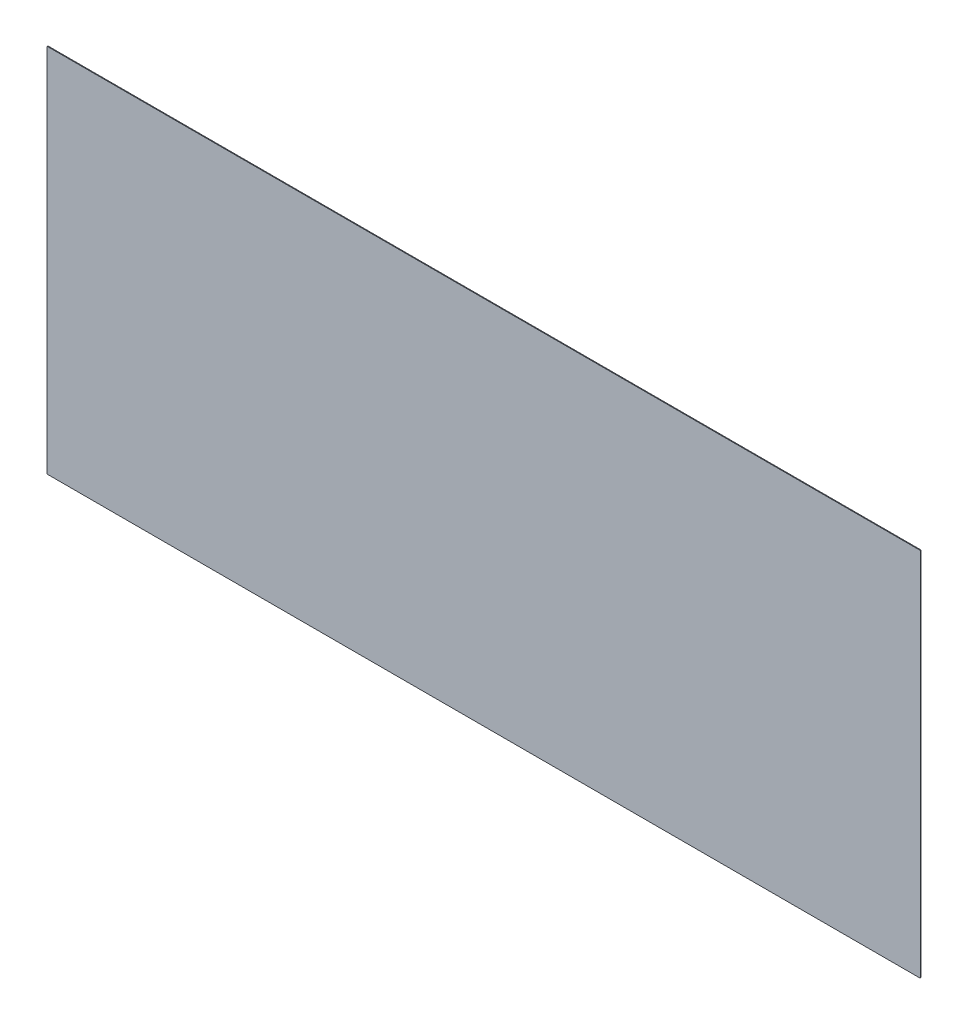
SolidWorks part; units mm, degrees
ref_plane "Front Plane" through (0, 0, 0) normal (0, 0, 1) x (1, 0, 0)
ref_plane "Top Plane" through (0, 0, 0) normal (0, 1, 0) x (1, 0, 0)
ref_plane "Right Plane" through (0, 0, 0) normal (1, 0, 0) x (0, 0, -1)
sketch "Sketch1" plane through (0, 0, 0) normal (0, 0, 1) x (1, 0, 0)
  line L1 (1, 0) -> (1159, 0)
  line L2 (0, 1) -> (0, 491)
  line L3 (1, 492) -> (1159, 492)
  line L4 (1160, 1) -> (1160, 491)
  arc A0 (1159, 492) -> (1160, 491) centre (1159, 491) cw
  arc A1 (1159, 0) -> (1160, 1) centre (1159, 1) ccw
  arc A2 (1, 0) -> (0, 1) centre (1, 1) cw
  arc A3 (0, 491) -> (1, 492) centre (1, 491) cw
  point P7 (1160, 492)
  point P10 (1160, 0)
  point P13 (0, 0)
  point P16 (0, 492)
  dimension "D3" = 1
  dimension "D1" = 1160
  dimension "D2" = 492
base flange "Base-Flange1" sketch "Sketch1" thickness 1 reverse thickness direction no parameters "D1"=2
sketch "Bend-Lines1" [suppressed] plane through (0, 0, 0) normal (0, 1, 0) x (1, 0, 0)
sketch "Bounding-Box1" [suppressed] plane through (0, 0, 0) normal (0, 1, 0) x (1, 0, 0)
sheet metal parameters "Sheet-Metal1" thickness 1 parameters "D1"=2
flat pattern "Flat-Pattern1" [suppressed]
sketch "Bend-Lines2" plane through (0, 0, 0) normal (0, 1, 0) x (1, 0, 0)
sketch3d "Bounding-Box2" [suppressed]
  line L0 (-1159, -491, 0) -> (1, -491, 0) construction
  line L1 (-1159, 1, 0) -> (1, 1, 0) construction
  line L2 (-1159, -491, 0) -> (-1159, 1, 0) construction
  line L3 (1, -491, 0) -> (1, 1, 0) construction
